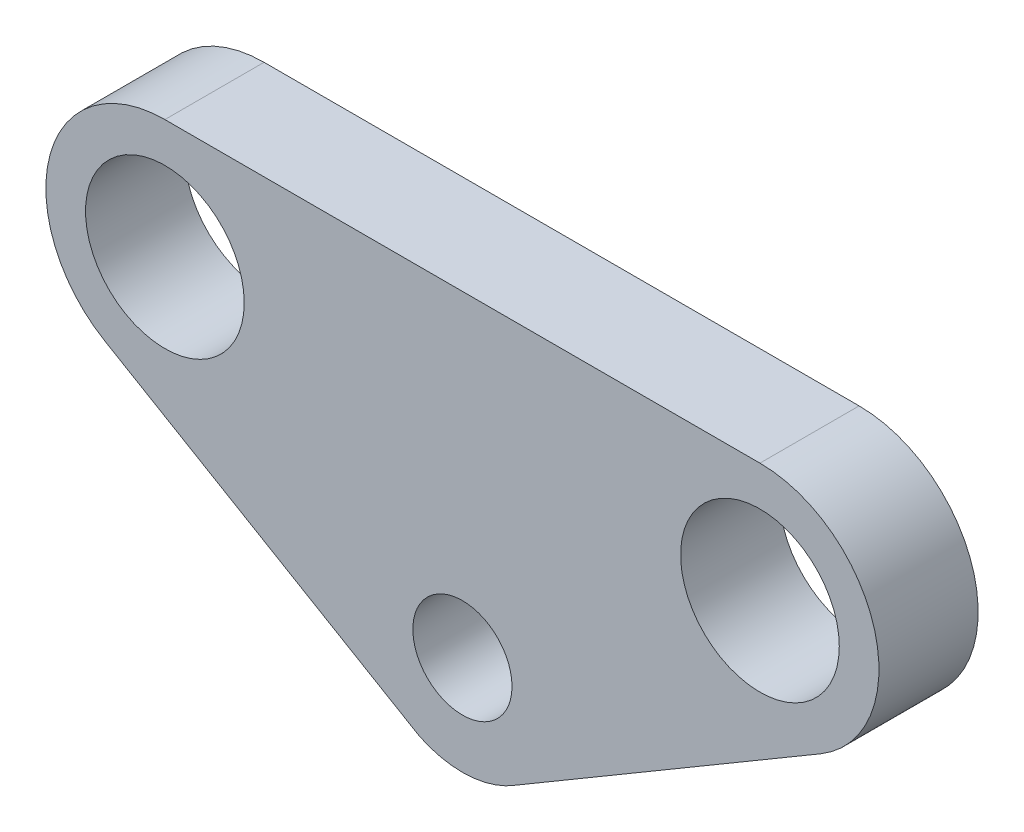
SolidWorks part; units mm, degrees
ref_plane "Front Plane" through (0, 0, 0) normal (0, 0, 1) x (1, 0, 0)
ref_plane "Top Plane" through (0, 0, 0) normal (0, 1, 0) x (1, 0, 0)
ref_plane "Right Plane" through (0, 0, 0) normal (1, 0, 0) x (0, 0, -1)
sketch "Sketch1" plane through (0, 0, 0) normal (0, 0, 1) x (1, 0, 0)
  line L0 (-15, 16) -> (15, 16)
  line L1 (0, 0) -> (0, 18.7938) construction
  line L11 (18.0454, 4.8303) -> (2.6787, -4.2219)
  line L12 (-18.0454, 4.8303) -> (-2.162, -4.5084)
  circle A0 centre (0, 0) radius 11.5 construction
  circle A1 centre (-15, 10) radius 11.5 construction
  circle A2 centre (15, 10) radius 11.5 construction
  circle A3 centre (-15, 10) radius 4
  arc A5 (-18.0454, 4.8303) -> (-15, 16) centre (-15, 10) cw
  circle A6 centre (15, 10) radius 4
  arc A7 (18.0454, 4.8303) -> (15, 16) centre (15, 10) ccw
  circle A8 centre (0, 0) radius 2.5
  circle A9 centre (0, 0) radius 5 construction
  arc A10 (-2.162, -4.5084) -> (2.6999, -4.2084) centre (0, 0) ccw
  point P21 (0, -12)
  dimension "D1" = 23
  dimension "D3" = 8
  dimension "D4" = 6
  dimension "D7" = 10
  dimension "D5" = 5
  dimension "D6" = 10
  dimension "D2" = 15
extrude "Boss-Extrude1" add sketch "Sketch1" along normal blind 5 contours A7 A5 A6 A3 region at (0.0021, 7.4864, 0)
